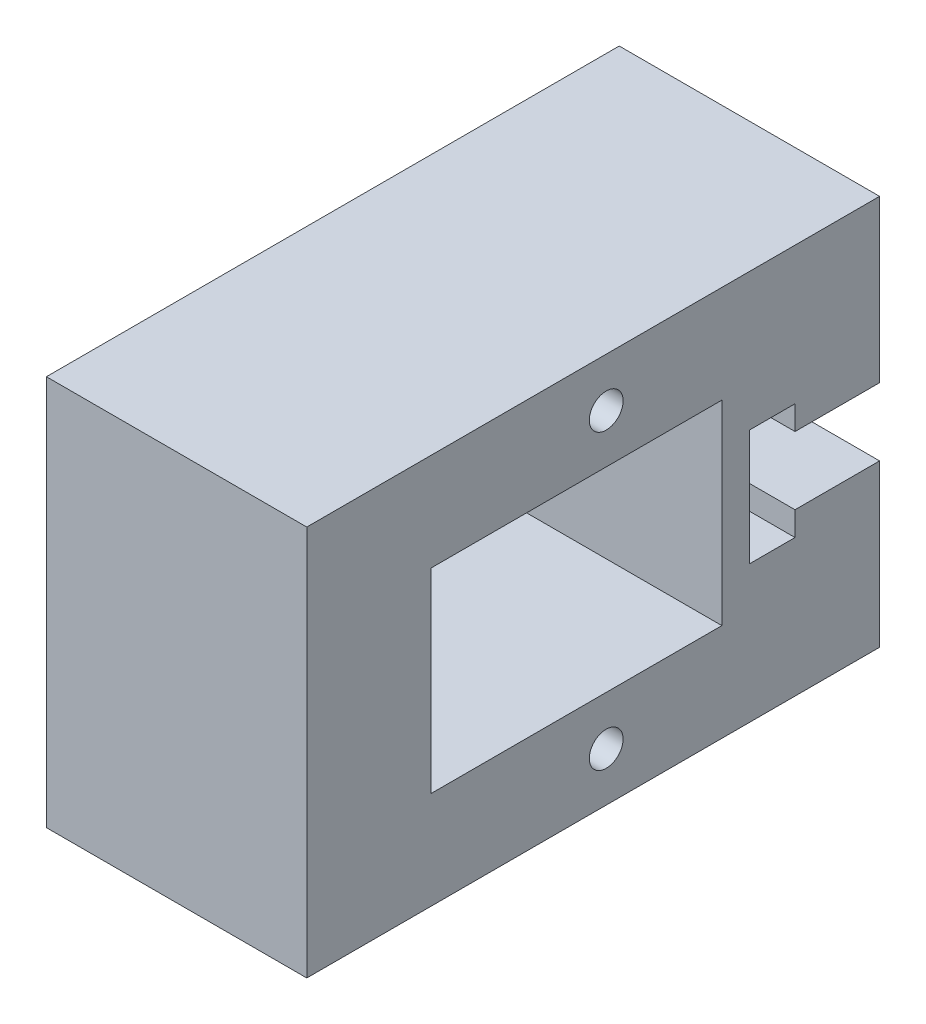
SolidWorks part; units mm, degrees
ref_plane "Front Plane" through (0, 0, 0) normal (1, 0, 0) x (0, 1, 0)
ref_plane "Top Plane" through (0, 0, 0) normal (0, 0, 1) x (0, 1, 0)
ref_plane "Right Plane" through (0, 0, 0) normal (0, 1, 0) x (-1, 0, 0)
sketch "Sketch1" plane through (0, 0, 0) normal (1, 0, 0) x (0, 1, 0)
  line L1 (0, 0) -> (38.1, 0)
  line L2 (0, 0) -> (0, 50.8)
  line L3 (0, 50.8) -> (38.1, 50.8)
  line L4 (38.1, 0) -> (38.1, 50.8)
  dimension "D1" = 50.8
  dimension "D2" = 38.1
extrude "Boss-Extrude1" add sketch "Sketch1" along normal blind 25.4
sketch "Sketch2" plane through (25.4, 0, 0) normal (1, 0, 0) x (0, 1, 0)
  line L0 (0, 0) -> (38.1, 0) construction
  line L1 (13.3985, 12.7) -> (24.7015, 12.7)
  line L2 (13.3985, 12.7) -> (13.3985, 8.2501)
  line L3 (13.3985, 8.2501) -> (15.748, 8.2501)
  line L4 (24.7015, 12.7) -> (24.7015, 8.2501)
  line L6 (15.748, 8.2501) -> (15.748, 0)
  line L7 (15.748, 0) -> (22.352, 0)
  line L8 (22.352, 8.2501) -> (22.352, 0)
  line L10 (22.352, 8.2501) -> (24.7015, 8.2501)
  point P5 (16.002, -0.5753)
  point P11 (16.002, 0)
  point P13 (22.352, 0)
  point P14 (0, 0)
  point P15 (24.7015, 8.255)
  point P16 (0, 0)
  point P18 (0, 0)
  point P19 (0, 0)
  point P20 (15.748, 8.255)
  point P21 (7.0485, 8.2501)
  point P22 (13.3985, 12.7)
extrude "Cut-Extrude1" cut sketch "Sketch2" against normal up to vertex (25.4 mm away)
sketch "Sketch3" plane through (25.4, 0, 0) normal (1, 0, 0) x (0, 1, 0)
  line L0 (24.7015, 12.7) -> (13.3985, 12.7) construction
  line L1 (3.175, 47.625) -> (34.925, 47.625)
  line L2 (3.175, 47.625) -> (3.175, 15.875)
  line L3 (3.175, 15.875) -> (34.925, 15.875)
  line L4 (34.925, 47.625) -> (34.925, 15.875)
  line L5 (38.1, 0) -> (38.1, 50.8) construction
  line L6 (0, 50.8) -> (0, 0) construction
  line L7 (38.1, 50.8) -> (0, 50.8) construction
  dimension "D1" = 3.175
  dimension "D2" = 3.175
  dimension "D3" = 3.175
  dimension "D4" = 3.175
extrude "Cut-Extrude2" cut sketch "Sketch3" against normal blind 21.59
sketch "Sketch4" plane through (0, 0, 15.875) normal (0, 0, 1) x (1, 0, 0)
  line L0 (3.81, 3.175) -> (3.81, 34.925) construction
  line L1 (3.81, 6.35) -> (16.51, 6.35)
  line L2 (3.81, 6.35) -> (3.81, 31.75)
  line L3 (3.81, 31.75) -> (16.51, 31.75)
  line L4 (16.51, 6.35) -> (16.51, 31.75)
  line L5 (3.81, 3.175) -> (25.4, 3.175) construction
  line L6 (3.81, 34.925) -> (25.4, 34.925) construction
  dimension "D1" = 12.7
  dimension "D2" = 3.175
  dimension "D3" = 3.175
sketch "Sketch5" plane through (0, 0, 0) normal (-1, 0, 0) x (0, -1, 0)
  line L0 (-6.35, 15.875) -> (-31.75, 15.875) construction
  line L1 (-19.05, 15.875) -> (-6.35, 15.875)
  line L2 (-19.05, 15.875) -> (-19.05, 28.575)
  line L3 (-19.05, 28.575) -> (-6.35, 28.575)
  line L4 (-6.35, 15.875) -> (-6.35, 28.575)
  line L5 (0, 50.8) -> (0, 0) construction
  dimension "D1" = 12.7
  dimension "D2" = 12.7
  dimension "D3" = 6.35
extrude "Cut-Extrude3" cut sketch "Sketch5" against normal up to vertex (3.81 mm away)
extrude "Cut-Extrude4" cut sketch "Sketch4" against normal up to vertex (3.175 mm away) contours L2 L3 L4 L1
sketch "Sketch6" plane through (25.4, 0, 0) normal (1, 0, 0) x (0, 1, 0)
  line L0 (34.925, 15.875) -> (34.925, 47.625) construction
  line L1 (3.175, 15.875) -> (9.525, 15.875)
  line L2 (3.175, 15.875) -> (3.175, 20.955)
  line L3 (3.175, 20.955) -> (9.525, 20.955)
  line L4 (9.525, 15.875) -> (9.525, 20.955)
  line L5 (34.925, 15.875) -> (28.575, 15.875)
  line L6 (34.925, 15.875) -> (34.925, 20.955)
  line L7 (34.925, 20.955) -> (28.575, 20.955)
  line L8 (28.575, 15.875) -> (28.575, 20.955)
  line L9 (3.175, 15.875) -> (34.925, 15.875) construction
  line L11 (3.175, 47.625) -> (34.925, 47.625)
  line L12 (3.175, 47.625) -> (3.175, 42.545)
  line L13 (3.175, 42.545) -> (34.925, 42.545)
  line L14 (34.925, 47.625) -> (34.925, 42.545)
  dimension "D1" = 6.35
  dimension "D2" = 6.35
  dimension "D3" = 5.08
  dimension "D4" = 5.08
extrude "Boss-Extrude2" add sketch "Sketch6" against normal up to vertex (25.4 mm away)
sketch "Sketch7" plane through (0, 0, 0) normal (-1, 0, 0) x (0, -1, 0)
  circle A0 centre (-20.066, 46.3038) radius 1.7145
  circle A1 centre (-5.334, 46.3038) radius 1.7145
  circle A2 centre (-4.4962, 16.002) radius 1.7145
  circle A3 centre (-20.9038, 16.002) radius 1.7145
extrude "Cut-Extrude5" cut sketch "Sketch7" against normal up to vertex
sketch "Sketch8" plane through (0, 0, 0) normal (-1, 0, 0) x (0, -1, 0)
  circle A0 centre (-20.066, 46.3038) radius 3.175
  circle A1 centre (-5.334, 46.3038) radius 3.175
  circle A2 centre (-4.4962, 16.002) radius 3.175
  circle A3 centre (-20.9038, 16.002) radius 3.175
  dimension "D1" = 6.35
  dimension "D2" = 6.35
  dimension "D3" = 6.35
  dimension "D4" = 6.35
extrude "Cut-Extrude6" cut sketch "Sketch8" against normal blind 18.796
sketch "Sketch9" plane through (0, 0, 0) normal (-1, 0, 0) x (0, -1, 0)
  circle A0 centre (-20.066, 37.8193) radius 3.175
  circle A1 centre (-5.334, 24.0542) radius 3.175
  circle A2 centre (-4.4962, 16.002) radius 3.175 construction
extrude "Cut-Extrude7" cut sketch "Sketch9" against normal up to vertex
sketch "Sketch10" plane through (25.4, 0, 0) normal (1, 0, 0) x (0, 1, 0)
  circle A0 centre (5.334, 24.0542) radius 4.826
  circle A1 centre (5.334, 24.0542) radius 3.175
  circle A2 centre (20.066, 37.8193) radius 4.7625
  circle A3 centre (20.066, 37.8193) radius 3.175
  dimension "D1" = 9.525
  dimension "D2" = 9.652
extrude "Boss-Extrude3" add sketch "Sketch10" against normal up to vertex (25.4 mm away)
sketch "Sketch11" plane through (0, 0, 0) normal (-1, 0, 0) x (0, -1, 0)
  circle A0 centre (-20.9038, 16.002) radius 3.175
  circle A1 centre (-4.4962, 16.002) radius 3.175
  circle A2 centre (-20.066, 46.3038) radius 3.175
  circle A3 centre (-5.334, 46.3038) radius 3.175
extrude "Boss-Extrude4" add sketch "Sketch11" against normal up to vertex (25.4 mm away)
sketch "Sketch12" plane through (25.4, 0, 0) normal (1, 0, 0) x (0, 1, 0)
  circle A0 centre (5.334, 24.0542) radius 3.175
  circle A1 centre (5.334, 24.0542) radius 1.651
  circle A2 centre (20.066, 37.8193) radius 3.175
  circle A3 centre (20.066, 37.8193) radius 1.651
  dimension "D1" = 6.35
  dimension "D2" = 6.35
  dimension "D3" = 3.302
  dimension "D4" = 3.302
extrude "Boss-Extrude5" add sketch "Sketch12" against normal blind 5
sketch "Sketch13" plane through (25.4, 0, 0) normal (1, 0, 0) x (0, 1, 0)
  line L0 (22.225, 42.0643) -> (22.225, 42.545) construction
  line L1 (20.6569, 42.545) -> (22.225, 42.545) construction
  line L2 (22.225, 42.0643) -> (22.225, 42.545)
  line L3 (20.6569, 42.545) -> (22.225, 42.545)
  arc A0 (22.225, 42.0643) -> (20.6569, 42.545) centre (20.066, 37.8193) ccw construction
  arc A1 (22.225, 42.0643) -> (20.6569, 42.545) centre (20.066, 37.8193) ccw
extrude "Boss-Extrude6" add sketch "Sketch13" against normal up to vertex (25.4 mm away)
sketch "Sketch14" plane through (25.4, 0, 0) normal (1, 0, 0) x (0, 1, 0)
  line L4 (18.415, 37.8193) -> (17.145, 37.8193) construction
  line L6 (19.4751, 42.545) -> (15.3035, 42.545)
  line L8 (15.3035, 37.8193) -> (15.3035, 42.545)
  circle A4 centre (20.066, 37.8193) radius 1.651 construction
  arc A6 (19.4751, 42.545) -> (22.225, 42.0643) centre (20.066, 37.8193) ccw construction
  arc A7 (19.4751, 42.545) -> (15.3035, 37.8193) centre (20.066, 37.8193) ccw
  dimension "D1" = 1.27
extrude "Boss-Extrude7" add sketch "Sketch14" against normal up to vertex (25.4 mm away)
sketch "Sketch15" plane through (0, 0, 50.8) normal (0, 0, 1) x (1, 0, 0)
  line L4 (0, 38.1) -> (0, 0)
  line L5 (0, 0) -> (25.4, 0)
  line L6 (25.4, 0) -> (25.4, 38.1)
  line L7 (25.4, 38.1) -> (0, 38.1)
  line L8 (0, 38.1) -> (0, 0)
  line L9 (0, 0) -> (25.4, 0)
  line L10 (25.4, 0) -> (25.4, 38.1)
  line L11 (25.4, 38.1) -> (0, 38.1)
  dimension "D1" = 0
extrude "Boss-Extrude8" add sketch "Sketch15" along normal blind 5.08
sketch "Sketch16" plane through (25.4, 0, 0) normal (1, 0, 0) x (0, 1, 0)
  line L0 (8.34, 43.415) -> (17.06, 43.415) construction
  line L1 (8.086, 43.669) -> (17.314, 43.669)
  line L2 (8.086, 43.669) -> (8.086, 40.0917)
  line L3 (8.086, 40.0917) -> (17.314, 40.0917)
  line L4 (17.314, 43.669) -> (17.314, 40.0917)
  line L5 (17.06, 43.415) -> (17.06, 30.9474) construction
  dimension "D1" = 0.254
  dimension "D2" = 0.254
  dimension "D3" = 0.254
extrude "Cut-Extrude9" cut sketch "Sketch16" against normal up to vertex
fillet "Fillet1" radius 30.48 1 edges at (14.605, 15.3035, 40.0917)
fillet "Fillet2" radius 2.54 1 edges at (14.605, 15.946, 35.4304)
sketch "Sketch17" plane through (25.4, 0, 0) normal (1, 0, 0) x (0, 1, 0)
  line L1 (3.175, 42.545) -> (34.925, 42.545)
  line L2 (3.175, 42.545) -> (3.175, 15.3861)
  line L3 (3.175, 15.3861) -> (34.925, 15.3861)
  line L4 (34.925, 42.545) -> (34.925, 15.3861)
extrude "Cut-Extrude10" cut sketch "Sketch17" against normal up to vertex
sketch "Sketch18" plane through (25.4, 0, 0) normal (1, 0, 0) x (0, 1, 0)
  line L1 (3.175, 42.545) -> (34.925, 42.545)
  line L2 (3.175, 42.545) -> (3.175, 43.7804)
  line L3 (3.175, 43.7804) -> (34.925, 43.7804)
  line L4 (34.925, 42.545) -> (34.925, 43.7804)
  point P5 (0, 0)
  point P7 (34.925, 43.7804)
extrude "Cut-Extrude11" cut sketch "Sketch18" against normal up to vertex
sketch "Sketch19" plane through (3.81, 0, 0) normal (1, 0, 0) x (0, 1, 0)
  line L0 (34.925, 43.7804) -> (3.175, 43.7804) construction
  line L1 (8.255, 43.7804) -> (3.175, 43.7804)
  line L2 (8.255, 43.7804) -> (8.255, 15.3861)
  line L3 (8.255, 15.3861) -> (3.175, 15.3861)
  line L4 (3.175, 43.7804) -> (3.175, 15.3861)
  line L6 (29.845, 43.7804) -> (34.925, 43.7804)
  line L7 (29.845, 43.7804) -> (29.845, 15.3861)
  line L8 (29.845, 15.3861) -> (34.925, 15.3861)
  line L9 (34.925, 43.7804) -> (34.925, 15.3861)
  dimension "D1" = 5.08
  dimension "D2" = 5.08
extrude "Boss-Extrude9" add sketch "Sketch19" along normal up to vertex (21.59 mm away)
sketch "Sketch20" plane through (25.4, 0, 0) normal (1, 0, 0) x (0, 1, 0)
  circle A0 centre (4.7625, 26.67) radius 1.651
  circle A1 centre (33.3375, 26.67) radius 1.651
  dimension "D1" = 3.302
  dimension "D2" = 3.302
extrude "Cut-Extrude12" cut sketch "Sketch20" against normal up to vertex (25.4 mm away)
sketch "Sketch21" plane through (0, 0, 0) normal (-1, 0, 0) x (0, -1, 0)
  circle A0 centre (-33.3375, 26.67) radius 3.0299
  circle A1 centre (-4.7625, 26.67) radius 3.429
  dimension "D1" = 6.858
sketch "Sketch22" plane through (0, 0, 0) normal (-1, 0, 0) x (0, -1, 0)
  line L2 (-7.0231, 28.575) -> (-8.255, 28.575)
  line L3 (-8.255, 28.575) -> (-8.255, 27.8959)
  line L4 (-7.0231, 28.575) -> (-8.255, 28.575)
  line L5 (-8.255, 28.575) -> (-8.255, 27.8959)
  arc A0 (-6.3677, 27.0563) -> (-3.175, 26.2165) centre (-4.7625, 26.67) ccw construction
  arc A1 (-6.3677, 27.0563) -> (-3.175, 26.2165) centre (-4.7625, 26.67) ccw
  arc A2 (-6.3677, 27.0563) -> (-3.1425, 26.3516) centre (-5.334, 24.0542) ccw construction
  arc A3 (-6.3677, 27.0563) -> (-3.1425, 26.3516) centre (-5.334, 24.0542) ccw
  arc A4 (-3.175, 26.2165) -> (-3.1425, 26.3516) centre (-4.7625, 26.67) ccw construction
  arc A5 (-7.0231, 28.575) -> (-8.255, 27.8959) centre (-5.334, 24.0542) ccw
  arc A6 (-7.0231, 28.575) -> (-8.255, 27.8959) centre (-5.334, 24.0542) ccw
  arc A7 (-3.175, 26.2165) -> (-3.1425, 26.3516) centre (-4.7625, 26.67) ccw
  dimension "D1" = 0
extrude "Boss-Extrude10" add sketch "Sketch22" against normal up to vertex (3.81 mm away)
sketch "Sketch23" plane through (3.81, 0, 0) normal (1, 0, 0) x (0, 1, 0)
  line L1 (8.255, 28.575) -> (29.845, 28.575)
  line L2 (8.255, 28.575) -> (8.255, 15.3861)
  line L3 (8.255, 15.3861) -> (29.845, 15.3861)
  line L4 (29.845, 28.575) -> (29.845, 15.3861)
extrude "Cut-Extrude13" cut sketch "Sketch23" against normal up to vertex (3.81 mm away)
sketch "Sketch24" plane through (3.81, 0, 0) normal (1, 0, 0) x (0, 1, 0)
  line L0 (8.255, 15.3861) -> (29.845, 15.3861) construction
  line L1 (29.845, 43.7804) -> (28.575, 43.7804)
  line L2 (29.845, 43.7804) -> (29.845, 15.3861)
  line L3 (29.845, 15.3861) -> (28.575, 15.3861)
  line L4 (28.575, 43.7804) -> (28.575, 15.3861)
  line L6 (8.255, 43.7804) -> (9.525, 43.7804)
  line L7 (8.255, 43.7804) -> (8.255, 15.3861)
  line L8 (8.255, 15.3861) -> (9.525, 15.3861)
  line L9 (9.525, 43.7804) -> (9.525, 15.3861)
  dimension "D1" = 1.27
  dimension "D2" = 1.27
extrude "Boss-Extrude13" add sketch "Sketch24" along normal up to vertex (21.59 mm away) and the other way up to vertex (3.81 mm away)
sketch "Sketch25" plane through (0, 31.75, 0) normal (0, -1, 0) x (1, 0, 0)
  line L4 (16.51, 15.3861) -> (3.81, 15.3861)
  line L5 (3.81, 15.3861) -> (3.81, 12.7)
  line L6 (3.81, 12.7) -> (16.51, 12.7)
  line L7 (16.51, 12.7) -> (16.51, 15.3861)
  line L8 (16.51, 15.3861) -> (3.81, 15.3861)
  line L9 (3.81, 15.3861) -> (3.81, 12.7)
  line L10 (3.81, 12.7) -> (16.51, 12.7)
  line L11 (16.51, 12.7) -> (16.51, 15.3861)
  dimension "D1" = 0
extrude "Boss-Extrude14" add sketch "Sketch25" along normal up to vertex (31.75 mm away)
